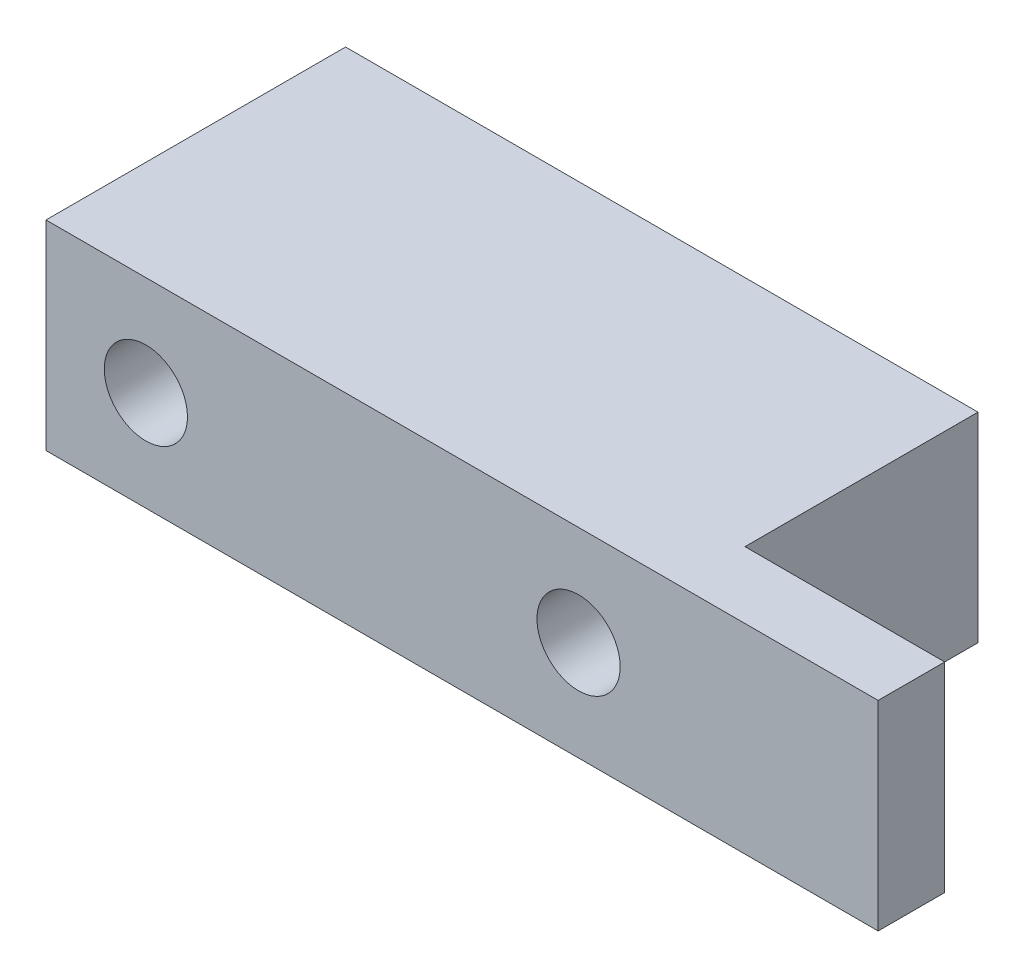
SolidWorks part; units mm, degrees
ref_plane "Front Plane" through (0, 0, 0) normal (1, 0, 0) x (0, 1, 0)
ref_plane "Top Plane" through (0, 0, 0) normal (0, 0, 1) x (0, 1, 0)
ref_plane "Right Plane" through (0, 0, 0) normal (0, 1, 0) x (-1, 0, 0)
sketch "Sketch1" plane through (0, 0, 0) normal (0, 0, 1) x (0, 1, 0)
  line L1 (-3, 9.5) -> (3, 9.5)
  line L2 (-3, 9.5) -> (-3, -9.5)
  line L3 (-3, -9.5) -> (3, -9.5)
  line L4 (3, 9.5) -> (3, -9.5)
  line L5 (-3, 9.5) -> (3, -9.5) construction
  line L6 (-3, -9.5) -> (3, 9.5) construction
  circle A0 centre (0, 6.5) radius 1.25
  circle A1 centre (0, -6.5) radius 1.25
  point P0 (0, 0)
  dimension "D3" = 2.5
  dimension "D4" = 2.5
  dimension "D5" = 3
  dimension "D6" = 3
  dimension "D7" = 3
  dimension "D1" = 19
  dimension "D2" = 6
  dimension "D8" = 3
extrude "Boss-Extrude1" add sketch "Sketch1" along normal blind 9
sketch "Sketch2" plane through (9.5, 0, 0) normal (1, 0, 0) x (0, 1, 0)
  line L0 (3, 9) -> (3, 0) construction
  line L1 (-3, 9) -> (3, 9)
  line L2 (-3, 9) -> (-3, 7)
  line L3 (-3, 7) -> (3, 7)
  line L4 (3, 9) -> (3, 7)
  dimension "D1" = 6
  dimension "D2" = 2
extrude "Boss-Extrude2" add sketch "Sketch2" along normal blind 6
